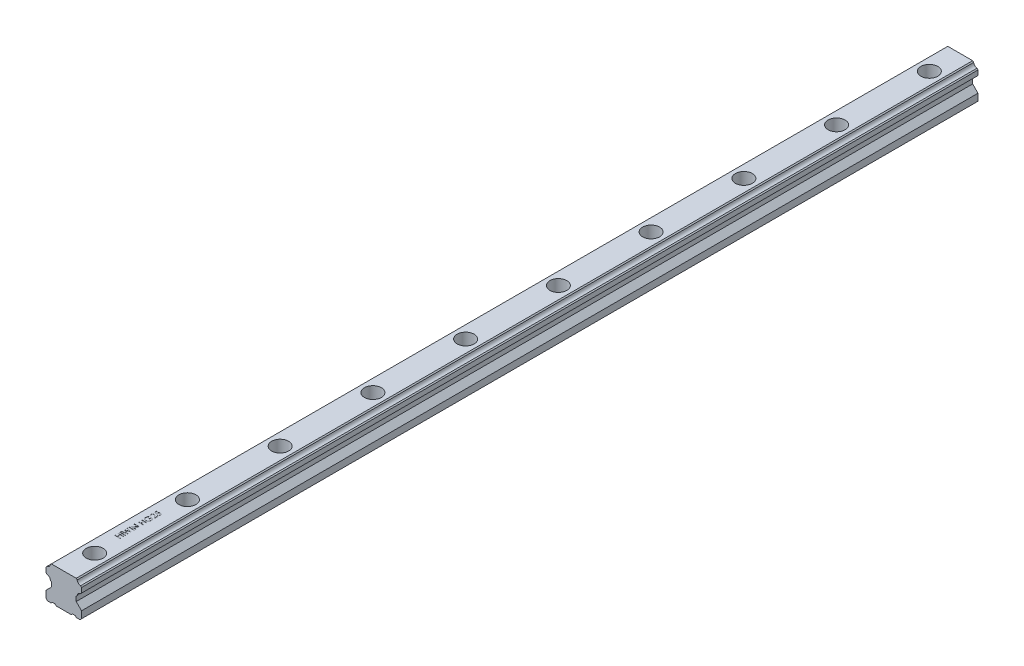
SolidWorks part; units mm, degrees
material "镀铬不锈钢"
ref_plane "前视基准面" through (0, 0, 0) normal (0, 0, 1) x (1, 0, 0)
ref_plane "上视基准面" through (0, 0, 0) normal (0, 1, 0) x (1, 0, 0)
ref_plane "右视基准面" through (0, 0, 0) normal (1, 0, 0) x (0, 0, -1)
sketch "草图1" plane through (0, 0, 0) normal (0, 0, 1) x (1, 0, 0)
  line L28 (8.05, 8.95) -> (8.05, 11.95)
  line L29 (-8.05, 22) -> (-8.6993, 21.3507)
  line L30 (-8.05, 11.95) -> (-8.05, 8.95)
  line L31 (-8.05, 8.95) -> (-11.5, 5.5)
  line L32 (11.5, 18.55) -> (10.8507, 19.1993)
  line L33 (11.5, 1) -> (11.5, 5.5)
  line L34 (5.6952, 0.7667) -> (7.4476, 0.7667)
  line L35 (8.05, 22) -> (-8.05, 22)
  line L36 (11.5, 5.5) -> (8.05, 8.95)
  line L37 (-8.6993, 12.5993) -> (-8.05, 11.95)
  line L38 (-5.6952, 0.7667) -> (-4.9286, 0)
  line L39 (8.6993, 21.3507) -> (8.05, 22)
  line L40 (10.5, 0) -> (11.5, 1)
  line L41 (-11.5, 15.4) -> (-10.8507, 14.7507)
  line L42 (-8.2143, 0) -> (-7.4476, 0.7667)
  line L43 (8.2143, 0) -> (10.5, 0)
  line L44 (-11.5, 18.55) -> (-11.5, 15.4)
  line L45 (11.5, 15.4) -> (11.5, 18.55)
  line L46 (10.8507, 14.7507) -> (11.5, 15.4)
  line L47 (-7.4476, 0.7667) -> (-5.6952, 0.7667)
  line L48 (-11.5, 1) -> (-10.5, 0)
  line L49 (-10.5, 0) -> (-8.2143, 0)
  line L50 (-4.9286, 0) -> (4.9286, 0)
  line L51 (4.9286, 0) -> (5.6952, 0.7667)
  line L52 (8.05, 11.95) -> (8.6993, 12.5993)
  line L53 (-10.8507, 19.1993) -> (-11.5, 18.55)
  line L54 (-11.5, 5.5) -> (-11.5, 1)
  line L55 (7.4476, 0.7667) -> (8.2143, 0)
  arc A4 (-8.6993, 12.5993) -> (-10.8507, 14.7507) centre (-10.9948, 12.4552) ccw
  arc A5 (-10.8507, 19.1993) -> (-8.6993, 21.3507) centre (-10.9948, 21.4948) ccw
  arc A6 (8.6993, 21.3507) -> (10.8507, 19.1993) centre (10.9948, 21.4948) ccw
  arc A7 (10.8507, 14.7507) -> (8.6993, 12.5993) centre (10.9948, 12.4552) ccw
extrude "凸台-拉伸1" add sketch "草图1" against normal blind 580
hole_wizard "M6 六角凹头螺钉的柱形沉头孔1" positions "草图3" profile "草图2" counterbore size "M6" standard "ISO" end condition through all
sketch "草图3" plane through (-2.7725, 22, -12.14) normal (0, 1, 0) x (-1, 0, 0)
  point P0 (-2.7725, -7.86)
  dimension "D1" = 20
sketch "草图2" plane through (0, 22, -20) normal (1, 0, 0) x (0, 0, 1)
  line L0 (0, 0) -> (0, 22)
  line L1 (0, 22) -> (3.5, 22)
  line L3 (3.5, 22) -> (3.5, 9)
  line L4 (3.5, 9) -> (5.5, 9)
  line L5 (5.5, 9) -> (5.5, 0)
  line L7 (5.5, 0) -> (0, 0)
  line L11 (0, -6.35) -> (0, 107.95) construction
  dimension "通孔孔直径" = 7
  dimension "通孔孔深度" = 22
  dimension "柱形沉头孔直径" = 11
  dimension "柱形沉头孔深度" = 9
pattern_linear "阵列(线性)1" count 10 spacing 60 along (0, 0, -1) of "M6 六角凹头螺钉的柱形沉头孔1"
sketch "草图6" plane through (0, 22, 0) normal (0, 1, 0) x (1, 0, 0)
  line L0 (0, 20) -> (0, 80) construction
  text T0 "HIWIN HG25"
extrude "切除-拉伸1" cut sketch "草图6" against normal blind 0.1
equation "\"D1@凸台-拉伸1\" = 2 * \"D1@草图3\" + \"D3@阵列(线性)1\" *  ( \"D1@阵列(线性)1\"  - 1) "
